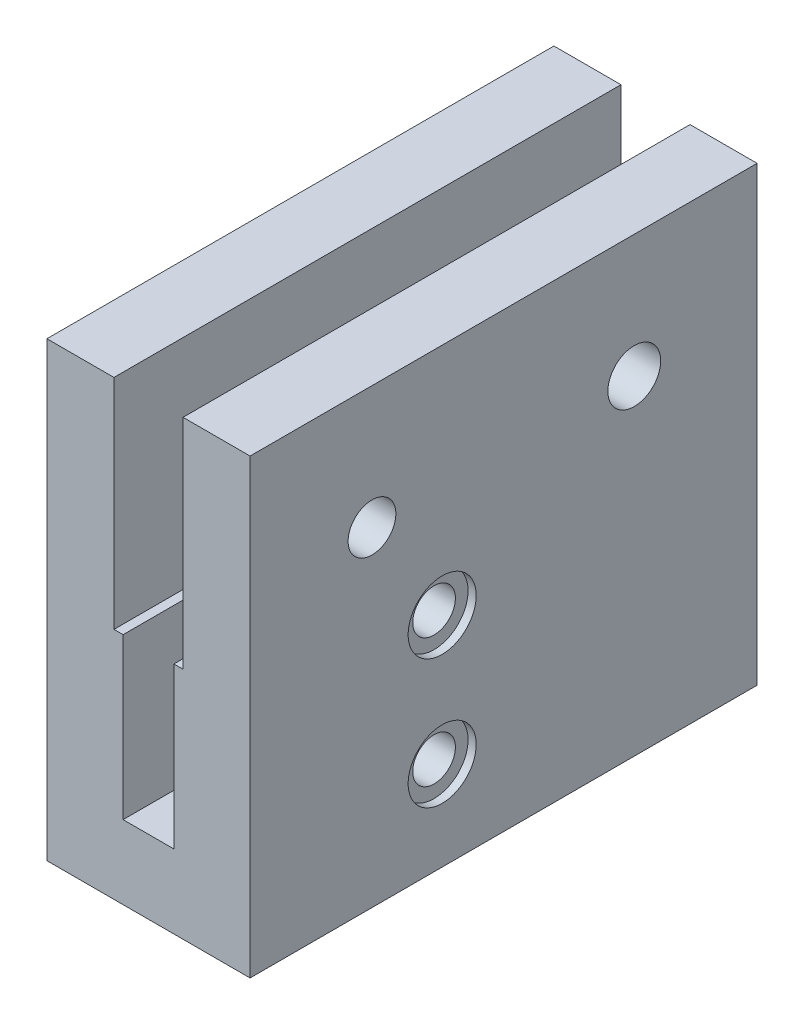
SolidWorks part; units mm, degrees
note: '?' marks a value the reader was unsure of. The reader was unsure of these and kept them because the rebuilt part matched: shared geometry of "Sketch9<3>".
ref_plane "Front Plane" through (0, 0, 0) normal (0, 0, 1) x (1, 0, 0)
ref_plane "Top Plane" through (0, 0, 0) normal (0, 1, 0) x (1, 0, 0)
ref_plane "Right Plane" through (0, 0, 0) normal (1, 0, 0) x (0, 0, -1)
sketch "Sketch2" plane through (0, 0, 0) normal (0, 1, 0) x (1, 0, 0)
  line L1 (-10, 24.955) -> (10, 24.955)
  line L2 (-10, 24.955) -> (-10, -24.955)
  line L3 (-10, -24.955) -> (10, -24.955)
  line L4 (10, 24.955) -> (10, -24.955)
  line L5 (-10, 24.955) -> (10, -24.955) construction
  line L6 (-10, -24.955) -> (10, 24.955) construction
  point P1 (0, 0)
  dimension "D1" = 20
  dimension "D2" = 49.91
extrude "Boss-Extrude1" add sketch "Sketch2" along normal blind 44.5
sketch "Sketch3" plane through (0, 0, 24.955) normal (0, 0, 1) x (1, 0, 0)
  line L0 (3.4, 44.5) -> (-3.4, 44.5)
  line L4 (3.4, 44.5) -> (3.4, 23.0202)
  line L6 (-10, 44.5) -> (10, 44.5) construction
  line L7 (-2.5, 7.2502) -> (2.5, 7.2502)
  line L8 (-2.5, 7.2502) -> (-2.5, 23.0202)
  line L10 (2.5, 7.2502) -> (2.5, 23.0202)
  line L14 (-3.4, 23.0202) -> (-2.5, 23.0202)
  line L15 (2.5, 23.0202) -> (3.4, 23.0202)
  line L16 (-3.4, 23.0202) -> (-3.4, 44.5)
  line L17 (0, 0) -> (0, 7.2502) construction
  line L18 (-10, 0) -> (10, 0) construction
  dimension "D1" = 6.8
  dimension "D2" = 21.4798
  dimension "D3" = 5
  dimension "D4" = 15.77
extrude "Cut-Extrude3" cut sketch "Sketch3" against normal through all
ref_axis "Axis1" through (2.5, 15.1352, 24.955) along (1, 0, 0)?
sketch "Sketch8" plane through (-10, 0, 0) normal (-1, 0, 0) x (0, 0, 1)
  line L3 (-24.955, 44.5) -> (-24.955, 23.0202) construction
  line L4 (24.955, 44.5) -> (24.955, 23.0202) construction
  line L6 (-24.955, 0) -> (24.955, 0) construction
  circle A0 centre (-12.865, 32.41) radius 2.6
  circle A1 centre (12.955, 32.41) radius 2.35
  dimension "D2" = 5.2
  dimension "D5" = 4.7
  dimension "D1" = 32.41
  dimension "D3" = 12.09
  dimension "D4" = 12
extrude "Cut-Extrude5" cut sketch "Sketch8" against normal through all and the other way through all
sketch "Sketch9" plane through (10, 0, 0) normal (1, 0, 0) x (0, 0, -1)
  line L0 (-6.045, 21.4852) -> (-24.955, 15.1352) construction
  line L1 (-24.955, 15.1352) -> (-6.045, 8.7852) construction
  circle A0 centre (-6.045, 21.4852) radius 2.1
  circle A1 centre (-6.045, 8.7852) radius 2.1
  circle A2 centre (-6.045, 21.4852) radius 3.35
  circle A3 centre (-6.045, 8.7852) radius 3.35
  dimension "D3" = 12.7
  dimension "D4" = 4.2
  dimension "D5" = 6.7
  dimension "D1" = 31
extrude "Cut-Extrude6" cut sketch "Sketch9" against normal blind 6.6
extrude "Cut-Extrude7" cut sketch "Sketch9<3>" against normal blind 0.8
sketch "Sketch9<3>" plane through (10, 0, 0) normal (1, 0, 0) x (0, 0, -1) same geometry as "Sketch9"
sketch "Sketch11" plane through (3.4, 0, 0) normal (-1, 0, 0) x (0, 0, 1)
  circle A0 centre (6.045, 21.4852) radius 3.35
  circle A1 centre (6.045, 8.7852) radius 3.35
  circle A2 centre (6.045, 21.4852) radius 2.1
  circle A3 centre (6.045, 8.7852) radius 2.1
  circle A4 centre (6.045, 21.4852) radius 3.35 construction
  circle A5 centre (6.045, 21.4852) radius 2.1 construction
extrude "Cut-Extrude8" cut sketch "Sketch11" against normal blind 0.8
sketch "Sketch12" plane through (0, 0, -24.955) normal (0, 0, -1) x (-1, 0, 0)
  line L1 (-3.4, 23.0202) -> (3.4, 23.0202)
  line L2 (-3.4, 23.0202) -> (-3.4, 7.2502)
  line L3 (-3.4, 7.2502) -> (3.4, 7.2502)
  line L4 (3.4, 23.0202) -> (3.4, 7.2502)
  line L6 (2.5, 7.2502) -> (-2.5, 7.2502) construction
extrude "Cut-Extrude9" cut sketch "Sketch12" against normal blind 15
